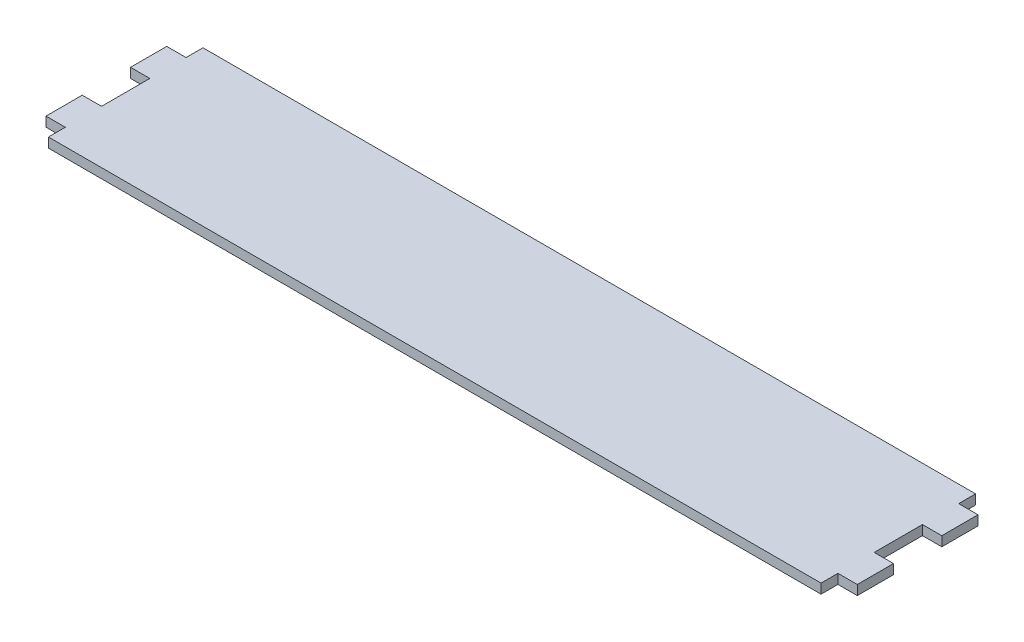
SolidWorks part; units mm, degrees
ref_plane "Front" through (0, 0, 0) normal (0, 0, 1) x (1, 0, 0)
ref_plane "Top" through (0, 0, 0) normal (0, 1, 0) x (1, 0, 0)
ref_plane "Right" through (0, 0, 0) normal (1, 0, 0) x (0, 0, -1)
sketch "Skizze1" plane through (0, 0, 0) normal (0, 1, 0) x (1, 0, 0)
  line L1 (160, 32) -> (-160, 32)
  line L2 (160, 32) -> (160, -32)
  line L3 (160, -32) -> (-160, -32)
  line L4 (-160, 32) -> (-160, -32)
  line L5 (160, 32) -> (-160, -32) construction
  line L6 (160, -32) -> (-160, 32) construction
  point P0 (0, 0)
  dimension "D1" = 320
  dimension "D2" = 64
extrude "Grundform" add sketch "Skizze1" along normal blind 4
sketch "Skizze2" plane through (0, 4, 0) normal (0, 1, 0) x (1, 0, 0)
  line L0 (0, 32) -> (0, 14) construction
  line L1 (160, 32) -> (-160, 32) construction
  line L2 (0, 14) -> (0, -14) construction
  line L3 (0, -14) -> (0, -32) construction
  line L4 (-160, -32) -> (160, -32) construction
  line L5 (0, -14) -> (-31, -14) construction
  line L6 (-31, -14) -> (-62, -14) construction
  line L7 (-62, -14) -> (-93, -14) construction
  line L8 (-93, -14) -> (-124, -14) construction
  line L10 (-15.5, 14) -> (-15.5, -14) construction
  line L11 (-15.5, 14) -> (0, 14) construction
  line L12 (-15.5, 14) -> (-46.5, 14) construction
  line L13 (-46.5, 14) -> (-77.5, 14) construction
  line L14 (-77.5, 14) -> (-108.5, 14) construction
  line L15 (-108.5, 14) -> (-139.5, 14) construction
  circle A0 centre (0, -14) radius 13.25
  circle A1 centre (-31, -14) radius 13.25
  circle A2 centre (-62, -14) radius 13.25
  circle A3 centre (-93, -14) radius 13.25
  circle A4 centre (-124, -14) radius 13.25
  circle A6 centre (-15.5, 14) radius 13.25
  circle A7 centre (-46.5, 14) radius 13.25
  circle A8 centre (-77.5, 14) radius 13.25
  circle A9 centre (-108.5, 14) radius 13.25
  circle A10 centre (-139.5, 14) radius 13.25
  circle A12 centre (124, -14) radius 13.25
  circle A13 centre (93, -14) radius 13.25
  circle A14 centre (62, -14) radius 13.25
  circle A15 centre (31, -14) radius 13.25
  circle A16 centre (139.5, 14) radius 13.25
  circle A17 centre (108.5, 14) radius 13.25
  circle A18 centre (77.5, 14) radius 13.25
  circle A19 centre (46.5, 14) radius 13.25
  circle A20 centre (15.5, 14) radius 13.25
  dimension "D1" = 26.5
  dimension "D2" = 18
  dimension "D3" = 31
extrude "Flaschendurchbruch" [suppressed] cut sketch "Skizze2" against normal through all
ref_plane "Ebene1" through (0, 0, 0) normal (1, 0, 0) x (0, 0, -1)
sketch "Skizze3" plane through (-160, 0, 0) normal (-1, 0, 0) x (0, 0, 1)
  line L0 (-32, 4) -> (32, 4) construction
  line L1 (-25, 4) -> (-10, 4)
  line L2 (-25, 4) -> (-25, 0)
  line L3 (-25, 0) -> (-10, 0)
  line L4 (-10, 4) -> (-10, 0)
  line L5 (-32, 0) -> (32, 0) construction
  line L6 (0, 0) -> (0, 4) construction
  line L11 (10, 4) -> (10, 0)
  line L12 (25, 0) -> (10, 0)
  line L13 (25, 4) -> (25, 0)
  line L14 (25, 4) -> (10, 4)
  dimension "D1" = 20
  dimension "D2" = 15
extrude "Aufsatz-Linear austragen2" add sketch "Skizze3" along normal blind 8
mirror "Spiegeln1" about plane through (0, 0, 0) normal (1, 0, 0) of "Aufsatz-Linear austragen2"
